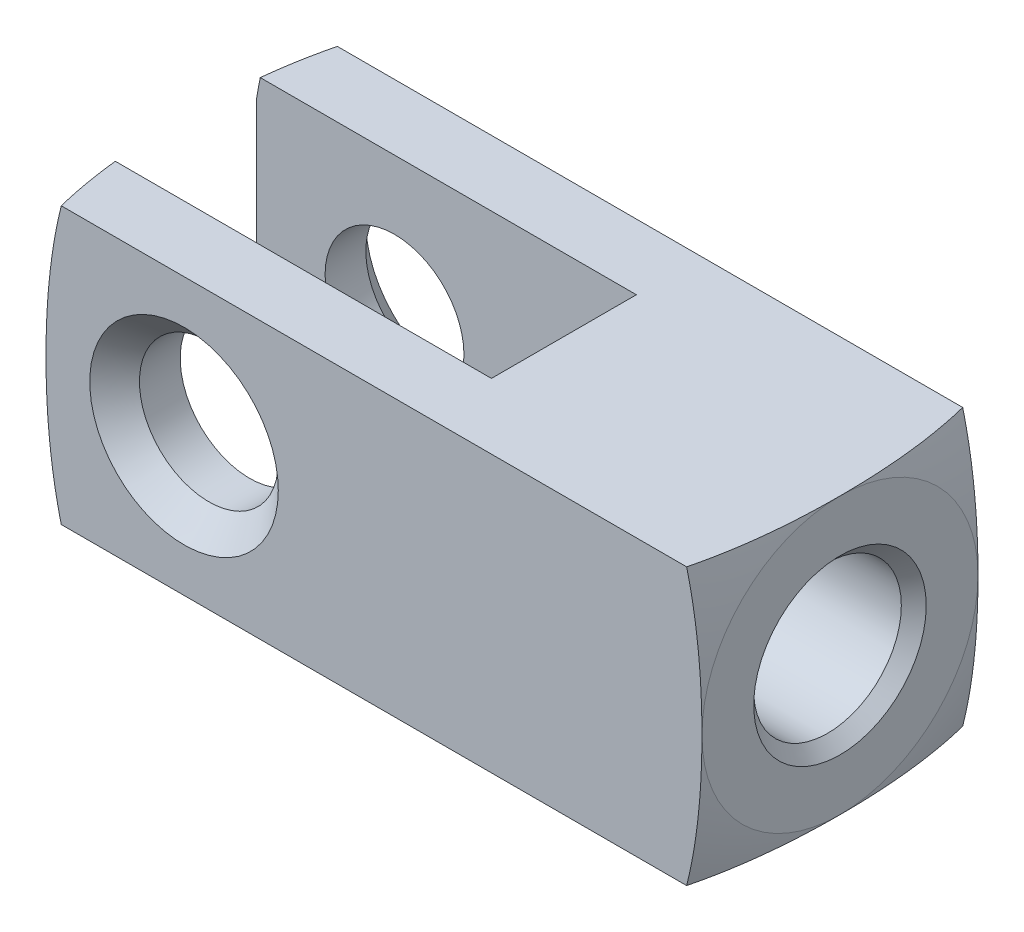
SolidWorks part; units mm, degrees
material "Cast Alloy Steel"
ref_plane "Front Plane" through (0, 0, 0) normal (0, 0, 1) x (1, 0, 0)
ref_plane "Top Plane" through (0, 0, 0) normal (0, 1, 0) x (1, 0, 0)
ref_plane "Right Plane" through (0, 0, 0) normal (1, 0, 0) x (0, 0, -1)
sketch "Sketch1" plane through (0, 0, 0) normal (0, 0, 1) x (1, 0, 0)
  line L0 (-6.35, 6.35) -> (-6.35, -6.35)
  line L1 (-6.35, -6.35) -> (23.8252, -6.35)
  line L2 (23.8252, -6.35) -> (23.8252, 6.35)
  line L3 (23.8252, 6.35) -> (-6.35, 6.35)
extrude "Boss-Extrude1" add sketch "Sketch1" against normal blind 6.35 and the other way blind 6.35
sketch "Sketch2" plane through (0, 0, 0) normal (0, 1, 0) x (1, 0, 0)
  line L0 (-6.35, 3.3338) -> (-6.35, -3.3338)
  line L1 (-6.35, -3.3338) -> (11.1252, -3.3338)
  line L2 (11.1252, -3.3338) -> (11.1252, 3.3338)
  line L3 (11.1252, 3.3338) -> (-6.35, 3.3338)
extrude "Cut-Extrude1" cut sketch "Sketch2" along normal blind 6.35 and the other way blind 6.35
hole_wizard "Hole1" positions "Sketch4" profile "Sketch3" legacy
sketch "Sketch4" plane through (23.8252, 0, 0) normal (1, 0, 0) x (0, 0, -1)
  point P0 (0, 0)
sketch "Sketch3" plane through (23.8252, 0, 0) normal (0, 1, 0) x (0, 0, -1)
  line L0 (0, 0) -> (0, 11.176)
  line L1 (0, 11.176) -> (3.396, 11.176)
  line L2 (3.396, 11.176) -> (3.396, 0.5728)
  line L3 (3.396, 0.5728) -> (3.9688, 0)
  line L4 (3.9688, 0) -> (0, 0)
  line L5 (0, -6.4453) -> (0, 115.525) construction
  line L6 (-3.396, 0.5728) -> (-3.9688, 0) construction
  dimension "Diameter" = 6.792
  dimension "Depth" = 11.176
  dimension "C-Sink Angle" = 90
  dimension "C-Sink Diameter" = 7.9375
cosmetic thread "Cosmetic Thread1" parameters "D1"=11.176, "D2"=7.9375
ref_plane "Plane1" through (0, 0, 6.35) normal (0, 0, 1) x (1, 0, 0)
ref_plane "Plane2" through (0, 0, -6.35) normal (0, 0, 1) x (1, 0, 0)
ref_plane "Plane3" through (23.876, 0, 0) normal (1, 0, 0) x (0, 0, -1)
hole_wizard "Hole2" positions "Sketch6" profile "Sketch5" legacy
sketch "Sketch6" plane through (12.6492, 0, 0) normal (1, 0, 0) x (0, 0, -1)
  point P0 (0, 0)
sketch "Sketch5" plane through (12.6492, 0, 0) normal (0, 1, 0) x (0, 0, -1)
  line L0 (0, 0) -> (0, 1.524)
  line L1 (0, 1.524) -> (3.396, 1.524)
  line L2 (3.396, 1.524) -> (3.396, 0)
  line L3 (3.396, 0) -> (0, 0)
  line L4 (0, 110) -> (0, -10) construction
  dimension "Diameter" = 6.792
  dimension "Depth" = 1.524
sketch "Sketch7" plane through (0, 0, 0) normal (1, 0, 0) x (0, 0, -1)
  line L0 (-6.35, 0) -> (-6.35, 4.337)
  line L1 (-6.35, 4.337) -> (-5.207, 3.194)
  line L2 (-5.207, 3.194) -> (5.207, 3.194)
  line L3 (5.207, 3.194) -> (6.35, 4.337)
  line L4 (6.35, 4.337) -> (6.35, 0)
  line L5 (6.35, 0) -> (-6.35, 0)
  line L6 (6.35, 0) -> (-6.35, 0) construction
revolve "Cut-Revolve1" cut sketch "Sketch7" angle 360 about L6 reverse direction yes
sketch "Sketch8" plane through (0, 0, 0) normal (0, 0, 1) x (1, 0, 0)
  line L0 (23.8252, 0) -> (23.8252, 6.35)
  line L1 (21.2852, 12.7) -> (30.1752, 12.7)
  line L2 (30.1752, 12.7) -> (30.1752, 0)
  line L3 (30.1752, 0) -> (23.8252, 0)
  line L4 (30.1752, 0) -> (23.8252, 0) construction
  arc A0 (23.8252, 6.35) -> (21.2852, 12.7) centre (6.6802, 3.175) ccw
revolve "Cut-Revolve2" cut sketch "Sketch8" angle 360 about L4 reverse direction yes
sketch "Sketch9" plane through (0, 0, 0) normal (0, 0, 1) x (1, 0, 0)
  line L0 (-12.7, 0) -> (-12.7, 12.7)
  line L1 (-12.7, 12.7) -> (-3.81, 12.7)
  line L2 (-6.35, 6.35) -> (-6.35, 0)
  line L3 (-6.35, 0) -> (-12.7, 0)
  line L4 (-6.35, 0) -> (-12.7, 0) construction
  arc A0 (-3.81, 12.7) -> (-6.35, 6.35) centre (10.795, 3.175) ccw
revolve "Cut-Revolve3" cut sketch "Sketch9" angle 360 about L4 reverse direction yes
ref_plane "Plane4" through (23.8252, 0, 0) normal (1, 0, 0) x (0, 0, -1)
ref_plane "Plane5" through (11.1252, 0, 0) normal (1, 0, 0) x (0, 0, -1)
ref_plane "dummy XY" through (0, 0, 0) normal (0, 0, 1) x (1, 0, 0)
ref_plane "dummy XZ" through (0, 0, 0) normal (0, -1, 0) x (-1, 0, 0)
ref_plane "dummy YZ" through (0, 0, 0) normal (1, 0, 0) x (0, 0, -1)
ref_axis "dummy X" through (-80.9, 0, 0) along (1, 0, 0)
ref_axis "dummy Y" through (0, -50, 0) along (0, 1, 0)
ref_axis "dummy Z" through (0, 0, 80.9) along (0, 0, -1)
sketch3d "dummy"
  point P0 (0, 0, 0)
ref_plane "h1 XY" through (0, 0, 0) normal (0, 0, 1) x (1, 0, 0)
ref_plane "h1 XZ" through (0, 6.35, 0) normal (0, -1, 0) x (-1, 0, 0)
ref_plane "h1 YZ" through (-6.35, 0, 0) normal (1, 0, 0) x (0, 0, -1)
ref_axis "h1 X" through (-80.9, 6.35, 0) along (1, 0, 0)
ref_axis "h1 Y" through (-6.35, -50, 0) along (0, 1, 0)
ref_axis "h1 Z" through (-6.35, 6.35, 80.9) along (0, 0, -1)
sketch3d "h1"
  point P0 (-6.35, 6.35, 0)
ref_plane "h2 XY" through (0, 0, 0) normal (0, 0, 1) x (1, 0, 0)
ref_plane "h2 XZ" through (0, -6.35, 0) normal (0, -1, 0) x (-1, 0, 0)
ref_plane "h2 YZ" through (-6.35, 0, 0) normal (1, 0, 0) x (0, 0, -1)
ref_axis "h2 X" through (-80.9, -6.35, 0) along (1, 0, 0)
ref_axis "h2 Y" through (-6.35, -50, 0) along (0, 1, 0)
ref_axis "h2 Z" through (-6.35, -6.35, 80.9) along (0, 0, -1)
sketch3d "h2"
  point P0 (-6.35, -6.35, 0)
ref_plane "l1 XY" through (0, 0, 0) normal (0, 0, 1) x (1, 0, 0)
ref_plane "l1 XZ" through (0, 6.35, 0) normal (0, -1, 0) x (-1, 0, 0)
ref_plane "l1 YZ" through (23.8252, 0, 0) normal (1, 0, 0) x (0, 0, -1)
ref_axis "l1 X" through (-80.9, 6.35, 0) along (1, 0, 0)
ref_axis "l1 Y" through (23.8252, -50, 0) along (0, 1, 0)
ref_axis "l1 Z" through (23.8252, 6.35, 80.9) along (0, 0, -1)
sketch3d "l1"
  point P0 (23.8252, 6.35, 0)
ref_plane "l11 XY" through (0, 0, 0) normal (0, 0, 1) x (1, 0, 0)
ref_plane "l11 XZ" through (0, 6.35, 0) normal (0, -1, 0) x (-1, 0, 0)
ref_plane "l11 YZ" through (23.8252, 0, 0) normal (1, 0, 0) x (0, 0, -1)
ref_axis "l11 X" through (-80.9, 6.35, 0) along (1, 0, 0)
ref_axis "l11 Y" through (23.8252, -50, 0) along (0, 1, 0)
ref_axis "l11 Z" through (23.8252, 6.35, 80.9) along (0, 0, -1)
sketch3d "l11"
  point P0 (23.8252, 6.35, 0)
ref_plane "l12 XY" through (0, 0, 0) normal (0, 0, 1) x (1, 0, 0)
ref_plane "l12 XZ" through (0, 6.35, 0) normal (0, -1, 0) x (-1, 0, 0)
ref_plane "l12 YZ" through (0, 0, 0) normal (1, 0, 0) x (0, 0, -1)
ref_axis "l12 X" through (-80.9, 6.35, 0) along (1, 0, 0)
ref_axis "l12 Y" through (0, -50, 0) along (0, 1, 0)
ref_axis "l12 Z" through (0, 6.35, 80.9) along (0, 0, -1)
sketch3d "l12"
  point P0 (0, 6.35, 0)
ref_plane "l2 XY" through (0, 0, 0) normal (0, 0, 1) x (1, 0, 0)
ref_plane "l2 XZ" through (0, 6.35, 0) normal (0, -1, 0) x (-1, 0, 0)
ref_plane "l2 YZ" through (-6.35, 0, 0) normal (1, 0, 0) x (0, 0, -1)
ref_axis "l2 X" through (-80.9, 6.35, 0) along (1, 0, 0)
ref_axis "l2 Y" through (-6.35, -50, 0) along (0, 1, 0)
ref_axis "l2 Z" through (-6.35, 6.35, 80.9) along (0, 0, -1)
sketch3d "l2"
  point P0 (-6.35, 6.35, 0)
ref_plane "l21 XY" through (0, 0, 0) normal (0, 1, 0) x (1, 0, 0)
ref_plane "l21 XZ" through (0, 0, 0) normal (0, 0, 1) x (1, 0, 0)
ref_plane "l21 YZ" through (23.8252, 0, 0) normal (1, 0, 0) x (0, 0, -1)
ref_axis "l21 X" through (-80.9, 0, 0) along (1, 0, 0)
ref_axis "l21 Y" through (23.8252, 0, 50) along (0, 0, -1)
ref_axis "l21 Z" through (23.8252, 50, 0) along (0, -1, 0)
sketch3d "l21"
  point P0 (23.8252, 0, 0)
ref_plane "l22 XY" through (0, 0, 0) normal (0, 1, 0) x (1, 0, 0)
ref_plane "l22 XZ" through (0, 0, 0) normal (0, 0, 1) x (1, 0, 0)
ref_plane "l22 YZ" through (11.1252, 0, 0) normal (1, 0, 0) x (0, 0, -1)
ref_axis "l22 X" through (-80.9, 0, 0) along (1, 0, 0)
ref_axis "l22 Y" through (11.1252, 0, 50) along (0, 0, -1)
ref_axis "l22 Z" through (11.1252, 50, 0) along (0, -1, 0)
sketch3d "l22"
  point P0 (11.1252, 0, 0)
ref_plane "piston_rod_clevis XY" through (23.8252, 0, 0) normal (1, 0, 0) x (0, 0, -1)
ref_plane "piston_rod_clevis XZ" through (0, 0, 0) normal (0, -1, 0) x (-1, 0, 0)
ref_plane "piston_rod_clevis YZ" through (0, 0, 0) normal (0, 0, -1) x (-1, 0, 0)
ref_axis "piston_rod_clevis X" through (23.8252, 0, 80.9) along (0, 0, -1)
ref_axis "piston_rod_clevis Y" through (23.8252, -50, 0) along (0, 1, 0)
ref_axis "piston_rod_clevis Z" through (80.9, 0, 0) along (-1, 0, 0)
sketch3d "piston_rod_clevis"
  point P0 (23.8252, 0, 0)
ref_plane "rod_clevis_body XY" through (0, 0, 0) normal (0, 0, 1) x (1, 0, 0)
ref_plane "rod_clevis_body XZ" through (0, 0, 0) normal (0, -1, 0) x (-1, 0, 0)
ref_plane "rod_clevis_body YZ" through (0, 0, 0) normal (1, 0, 0) x (0, 0, -1)
ref_axis "rod_clevis_body X" through (-80.9, 0, 0) along (1, 0, 0)
ref_axis "rod_clevis_body Y" through (0, -50, 0) along (0, 1, 0)
ref_axis "rod_clevis_body Z" through (0, 0, 80.9) along (0, 0, -1)
sketch3d "rod_clevis_body"
  point P0 (0, 0, 0)
ref_plane "th1 XY" through (0, 0, 0) normal (0, 0, 1) x (1, 0, 0)
ref_plane "th1 XZ" through (0, 3.9688, 0) normal (0, -1, 0) x (-1, 0, 0)
ref_plane "th1 YZ" through (23.8252, 0, 0) normal (1, 0, 0) x (0, 0, -1)
ref_axis "th1 X" through (-80.9, 3.9688, 0) along (1, 0, 0)
ref_axis "th1 Y" through (23.8252, -50, 0) along (0, 1, 0)
ref_axis "th1 Z" through (23.8252, 3.9688, 80.9) along (0, 0, -1)
sketch3d "th1"
  point P0 (23.8252, 3.9688, 0)
ref_plane "th2 XY" through (0, 0, 0) normal (0, 0, 1) x (1, 0, 0)
ref_plane "th2 XZ" through (0, -3.9688, 0) normal (0, -1, 0) x (-1, 0, 0)
ref_plane "th2 YZ" through (23.8252, 0, 0) normal (1, 0, 0) x (0, 0, -1)
ref_axis "th2 X" through (-80.9, -3.9688, 0) along (1, 0, 0)
ref_axis "th2 Y" through (23.8252, -50, 0) along (0, 1, 0)
ref_axis "th2 Z" through (23.8252, -3.9688, 80.9) along (0, 0, -1)
sketch3d "th2"
  point P0 (23.8252, -3.9688, 0)
ref_plane "to_cylinder XY" through (11.1252, 0, 0) normal (1, 0, 0) x (0, 0, -1)
ref_plane "to_cylinder XZ" through (0, 0, 0) normal (0, -1, 0) x (-1, 0, 0)
ref_plane "to_cylinder YZ" through (0, 0, 0) normal (0, 0, -1) x (-1, 0, 0)
ref_axis "to_cylinder X" through (11.1252, 0, 80.9) along (0, 0, -1)
ref_axis "to_cylinder Y" through (11.1252, -50, 0) along (0, 1, 0)
ref_axis "to_cylinder Z" through (80.9, 0, 0) along (-1, 0, 0)
sketch3d "to_cylinder"
  point P0 (11.1252, 0, 0)
ref_plane "w1 XY" through (0, 0, 0) normal (0, 1, 0) x (1, 0, 0)
ref_plane "w1 XZ" through (0, 0, -6.35) normal (0, 0, 1) x (1, 0, 0)
ref_plane "w1 YZ" through (23.8252, 0, 0) normal (1, 0, 0) x (0, 0, -1)
ref_axis "w1 X" through (-80.9, 0, -6.35) along (1, 0, 0)
ref_axis "w1 Y" through (23.8252, 0, 50) along (0, 0, -1)
ref_axis "w1 Z" through (23.8252, 50, -6.35) along (0, -1, 0)
sketch3d "w1"
  point P0 (23.8252, 0, -6.35)
ref_plane "w11 XY" through (0, 0, 0) normal (0, 1, 0) x (1, 0, 0)
ref_plane "w11 XZ" through (0, 0, -3.3338) normal (0, 0, 1) x (1, 0, 0)
ref_plane "w11 YZ" through (-6.35, 0, 0) normal (1, 0, 0) x (0, 0, -1)
ref_axis "w11 X" through (-80.9, 0, -3.3338) along (1, 0, 0)
ref_axis "w11 Y" through (-6.35, 0, 50) along (0, 0, -1)
ref_axis "w11 Z" through (-6.35, 50, -3.3338) along (0, -1, 0)
sketch3d "w11"
  point P0 (-6.35, 0, -3.3338)
ref_plane "w12 XY" through (0, 0, 0) normal (0, 1, 0) x (1, 0, 0)
ref_plane "w12 XZ" through (0, 0, 3.3338) normal (0, 0, 1) x (1, 0, 0)
ref_plane "w12 YZ" through (-6.35, 0, 0) normal (1, 0, 0) x (0, 0, -1)
ref_axis "w12 X" through (-80.9, 0, 3.3338) along (1, 0, 0)
ref_axis "w12 Y" through (-6.35, 0, 50) along (0, 0, -1)
ref_axis "w12 Z" through (-6.35, 50, 3.3338) along (0, -1, 0)
sketch3d "w12"
  point P0 (-6.35, 0, 3.3338)
ref_plane "w2 XY" through (0, 0, 0) normal (0, 1, 0) x (1, 0, 0)
ref_plane "w2 XZ" through (0, 0, 6.35) normal (0, 0, 1) x (1, 0, 0)
ref_plane "w2 YZ" through (23.8252, 0, 0) normal (1, 0, 0) x (0, 0, -1)
ref_axis "w2 X" through (-80.9, 0, 6.35) along (1, 0, 0)
ref_axis "w2 Y" through (23.8252, 0, 50) along (0, 0, -1)
ref_axis "w2 Z" through (23.8252, 50, 6.35) along (0, -1, 0)
sketch3d "w2"
  point P0 (23.8252, 0, 6.35)
